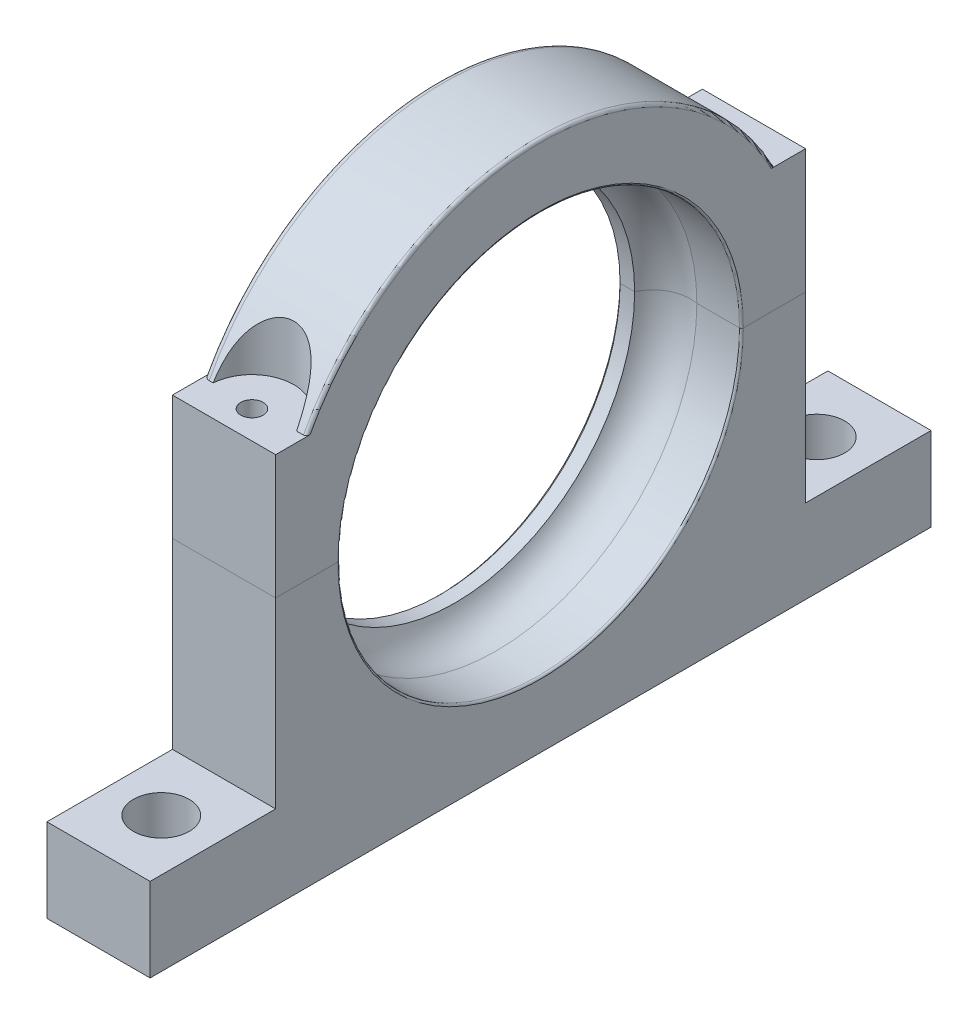
SolidWorks part; units mm, degrees
ref_plane "Plan de face" through (0, 0, 0) normal (0, 0, 1) x (1, 0, 0)
ref_plane "Plan de dessus" through (0, 0, 0) normal (0, 1, 0) x (1, 0, 0)
ref_plane "Plan de droite" through (0, 0, 0) normal (1, 0, 0) x (0, 0, -1)
sketch "Esquisse1" plane through (0, 0, 0) normal (0, 0, 1) x (1, 0, 0)
  line L0 (0, 92.9) -> (0, 65.5)
  line L1 (0, 65.5) -> (1.05, 64.45)
  line L2 (1.05, 64.45) -> (6.269, 64.45)
  line L3 (21.0021, 72.01) -> (36.3, 72.01)
  line L4 (37, 72.71) -> (37, 93.9)
  line L5 (35.9, 95) -> (2.1, 95)
  line L6 (-0.0013, 0) -> (37.0013, 0) construction
  arc A0 (2.1, 95) -> (0, 92.9) centre (2.1, 92.9) ccw
  arc A1 (6.269, 64.45) -> (21.0021, 72.01) centre (18.5, 58.75) cw
  arc A2 (36.3, 72.01) -> (37, 72.71) centre (36.3, 72.71) ccw
  arc A3 (37, 93.9) -> (35.9, 95) centre (35.9, 93.9) ccw
  point P2 (0, 0)
  dimension "D1" = 27.4
  dimension "D2" = 33.8
  dimension "D4" = 1.4849
  dimension "D8" = 1.5556
  dimension "D9" = 2.9699
revolve "Révolution1" add sketch "Esquisse1" angle 360 about L6 reverse direction yes
sketch "Esquisse2" plane through (0, 0, 0) normal (-1, 0, 0) x (0, 0, 1)
  line L0 (0, 0) -> (-116.9324, 0) construction
  line L1 (0, 0) -> (92.9, 0) construction
  line L2 (0, 0) -> (0, -89.4816) construction
  line L3 (14.4797, -95.5) -> (-102.4526, -95.5) construction
  line L4 (14.4797, -95.5) -> (138.829, -95.5) construction
  line L5 (0, -65.5) -> (155.3397, -65.5) construction
  line L6 (0, -65.5) -> (-123.2378, -65.5) construction
  line L8 (-95, -65.5) -> (-140, -65.5)
  line L9 (-140, -65.5) -> (-140, -95.5)
  line L10 (-140, -95.5) -> (140, -95.5)
  line L11 (140, -95.5) -> (140, -65.5)
  line L13 (95, -65.5) -> (140, -65.5)
  line L16 (-95, -65.5) -> (-95, 44.5)
  line L17 (-95, 44.5) -> (-81.5485, 44.5)
  line L18 (95, -65.5) -> (95, 44.5)
  line L19 (95, 44.5) -> (81.5485, 44.5)
  line L20 (92.9, 0) -> (95, 0) construction
  line L21 (95, 0) -> (112.4949, 0) construction
  circle A1 centre (0, 0) radius 65.5 construction
  circle A2 centre (0, 0) radius 92.9 construction
  arc A3 (-92.9, 0) -> (92.9, 0) centre (0, 0) ccw
  circle A5 centre (0, 0) radius 95 construction
  arc A6 (-81.5485, 44.5) -> (81.5485, 44.5) centre (0, 0) ccw
  point P7 (0, 0)
  circle M12 centre (0, 0) radius 92.9
  dimension "D1" = 45
  dimension "D2" = 30
  dimension "D3" = 110
extrude "Boss.-Extru.2" add sketch "Esquisse2" against normal blind 37 contours L18 L19 L17 L16 L8 L9 L10 L11 L13 M12 region at (0, -10.5, -94.687)
sketch "Esquisse4" plane through (0, 44.5, 0) normal (0, 1, 0) x (1, 0, 0)
  line L0 (37, 85) -> (0, 85) construction
  line L1 (37, 95) -> (37, 82.6859) construction
  line L2 (0, 95) -> (0, 81.5485) construction
  line L3 (37, 95) -> (0, 95) construction
  circle A0 centre (18.5, 85) radius 15
  point P10 (18.5, 95)
  dimension "D1" = 30
  dimension "D2" = 10
extrude "Enlèv. mat.-Extru.1" cut sketch "Esquisse4" along normal blind 37 contours A0
sketch "Esquisse6" plane through (0, 44.5, 0) normal (0, 1, 0) x (1, 0, 0)
  line L0 (37, 95) -> (0, 95) construction
  line L1 (0, 95) -> (0, 81.5485) construction
  circle A0 centre (18.5, 85) radius 4
  dimension "D2" = 8
  dimension "D1" = 10
  dimension "D3" = 18.5
extrude "Enlèv. mat.-Extru.2" cut sketch "Esquisse6" against normal blind 100
sketch "Esquisse7" plane through (0, -65.5, 0) normal (0, 1, 0) x (1, 0, 0)
  line L0 (0, 117.5) -> (37, 117.5) construction
  line L3 (18.5, 140) -> (18.5, 95) construction
  line L4 (37, 140) -> (0, 140) construction
  line L5 (37, 95) -> (0, 95) construction
  line L6 (0, 95) -> (0, 140) construction
  line L7 (37, 95) -> (37, 140) construction
  circle A0 centre (18.5, 117.5) radius 10
  dimension "D1" = 20
extrude "Enlèv. mat.-Extru.3" cut sketch "Esquisse7" against normal through all
mirror "Symétrie1" about plane through (0, 0, 0) normal (0, 0, 1) of "Enlèv. mat.-Extru.3", "Enlèv. mat.-Extru.2", "Enlèv. mat.-Extru.1"
sketch "Esquisse8" plane through (37, 0, 0) normal (1, 0, 0) x (0, 0, -1)
  line L0 (-95, 0) -> (95, 0)
  line L1 (-95, -65.5) -> (-95, 44.5) construction
  line L2 (95, -65.5) -> (95, 44.5) construction
split "Fractionner2" trim tools "Esquisse8" bodies to split 110 resulting bodies 112 113
